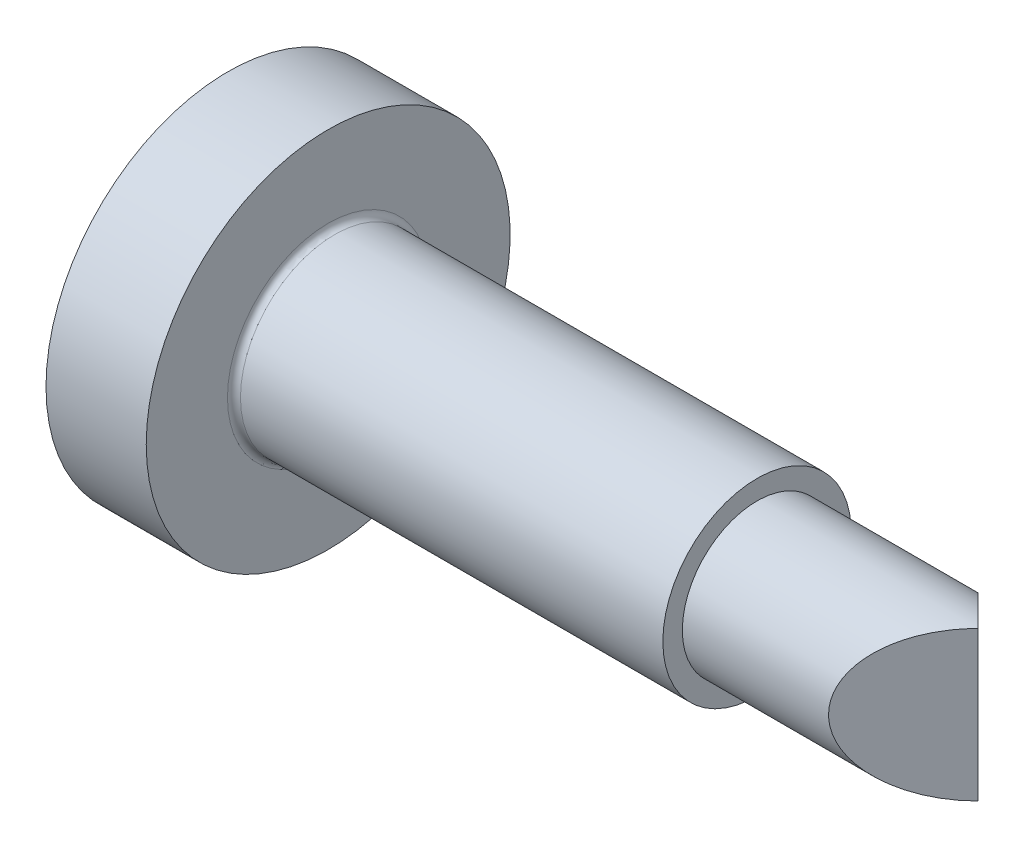
SolidWorks part; units mm, degrees
ref_plane "Front" through (0, 0, 0) normal (0, 0, 1) x (1, 0, 0)
ref_plane "Top" through (0, 0, 0) normal (0, 1, 0) x (1, 0, 0)
ref_plane "Right" through (0, 0, 0) normal (1, 0, 0) x (0, 0, -1)
sketch "Sketch1" plane through (0, 0, 0) normal (0, 0, 1) x (1, 0, 0)
  line L0 (-43.1593, 0) -> (76.0967, 0) construction
  line L1 (2.4, 1.45) -> (9, 1.45)
  line L2 (9, 1.45) -> (9, 1.15)
  line L3 (9, 1.15) -> (12.4, 1.15)
  line L4 (12.4, 1.15) -> (12.4, 0)
  line L5 (2.4, 1.45) -> (2.4, 2.8)
  line L6 (2.4, 2.8) -> (0.8575, 2.8)
  line L7 (12.4, 0) -> (0, 0)
  line L8 (3.5, 4.9815) -> (3.5, -1.8643) construction
  arc A0 (0.8575, 2.8) -> (0, 0) centre (5, 0) ccw
revolve "Base" add sketch "Sketch1" angle 360 about L0
cosmetic thread "ThreadCosmetic1" [suppressed] parameters "D1"=6.6, "D2"=2.3
fillet "Fillet1" radius 0.1 1 edges at (2.4, 0, 1.45)
sketch "Sketch2" plane through (0, 0, 0) normal (0, 1, 0) x (1, 0, 0)
  line L0 (7.7693, 0) -> (13.786, 0) construction
  line L2 (12.4, 0) -> (11.25, 1.15)
  line L4 (11.25, 1.15) -> (11.25, 1.8746)
  line L5 (11.25, 1.8746) -> (12.7585, 1.8746)
  line L6 (12.7585, 1.8746) -> (12.7585, -1.8746)
  line L8 (11.25, -1.8746) -> (12.7585, -1.8746)
  line L9 (11.25, -1.15) -> (11.25, -1.8746)
  line L10 (12.4, 0) -> (11.25, -1.15)
  line L11 (12.4, -1.15) -> (12.4, 1.15) construction
  line L12 (12.4, 1.15) -> (9, 1.15) construction
  point P14 (12.7585, 0)
  dimension "D1" = 45
  dimension "D2" = 0.7246
  dimension "D3" = 0.3585
extrude "Cut-Extrude1" cut sketch "Sketch2" against normal through all and the other way through all
sketch "Sketch3" plane through (0, 0, 0) normal (1, 0, 0) x (0, 0, -1)
  line L0 (-3.4533, 0) -> (3.7479, 0) construction
  line L1 (0, 3.3142) -> (0, -3.2487) construction
  line L2 (-0.3, 0.3) -> (-1.5, 0.3)
  line L3 (0.3, -1.5) -> (-0.3, -1.5)
  line L4 (0.3, -1.5) -> (0.3, -0.3)
  line L5 (0.3, 1.5) -> (-0.3, 1.5)
  line L6 (-0.3, -1.5) -> (-0.3, -0.3)
  line L7 (1.5, 0.3) -> (0.3, 0.3)
  line L8 (1.5, 0.3) -> (1.5, -0.3)
  line L9 (1.5, -0.3) -> (0.3, -0.3)
  line L10 (-1.5, 0.3) -> (-1.5, -0.3)
  line L11 (0.3, 0.3) -> (0.3, 1.5)
  line L12 (-0.3, 0.3) -> (-0.3, 1.5)
  line L13 (-0.3, -0.3) -> (-1.5, -0.3)
  dimension "D1" = 3
  dimension "D3" = 0.6
  dimension "D4" = 0.6
extrude "CrossRecess" cut sketch "Sketch3" along normal blind 0.8
fillet "Fillet2" radius 0.3 4 edges at (0.409, 0.3, 0.3) (0.409, 0.3, -0.3) (0.409, -0.3, 0.3) (0.409, -0.3, -0.3)
draft "Draft1" type of draft neutral plane draft angle 25 neutral plane "Right" faces to draft 4 face at (0.5175, -1.5, 0) face at (0.5175, 0, -1.5) face at (0.5175, 0, 1.5) face at (0.5175, 1.5, 0) neutral plane through (0, 0, 0) neutral plane normal (1, 0, 0) reverse direction yes parameters "D1"=25
sketch "Sketch4" plane through (0, 0, 0) normal (1, 0, 0) x (0, 0, -1)
  line L0 (-13.501, 0) -> (14.0755, 0) construction
  line L1 (0, -11.8062) -> (0, 13.0127) construction
  line L2 (0, 0) -> (-7.5165, 7.5165) construction
  line L3 (0, 0) -> (7.3653, 7.3653) construction
  line L4 (0, 0.4483) -> (1.0607, 1.0607)
  line L5 (0, 0.4483) -> (-1.0607, 1.0607)
  line L6 (1.0607, 1.0607) -> (0.4483, 0)
  line L7 (-1.0607, 1.0607) -> (-0.4483, 0)
  line L8 (-1.0607, -1.0607) -> (-0.4483, 0)
  line L9 (1.0607, -1.0607) -> (0.4483, 0)
  line L10 (0, -0.4483) -> (-1.0607, -1.0607)
  line L11 (0, -0.4483) -> (1.0607, -1.0607)
  dimension "D1" = 45
  dimension "D2" = 15
  dimension "D3" = 3
extrude "Cut-Extrude3" cut sketch "Sketch4" along normal blind 0.8
sketch "Sketch5" plane through (0, 0, 0) normal (0, 0, 1) x (1, 0, 0)
  line L0 (3.3268, 1.7964) -> (3.6732, 1.7964)
  line L1 (3.6732, 1.7964) -> (3.6732, 1.45)
  line L2 (3.6732, 1.45) -> (3.5, 1.15)
  line L3 (3.5, 1.15) -> (3.3268, 1.45)
  line L4 (3.3268, 1.7964) -> (3.3268, 1.45)
  line L5 (0, 0) -> (5.8873, 0) construction
  line L6 (2.4, -2.8) -> (2.4, 2.8) construction
  dimension "D2" = 2.3
  dimension "D1" = 2.9
  dimension "D3" = 1.1
revolve "Cut-Revolve10" [suppressed] cut sketch "Sketch5" angle 360 about L5
pattern_linear "LPattern10" [suppressed] count 13 spacing 0.45 along (1, 0, 0) of bodies 105
equation "\"D4@Sketch3\" = \"D3@Sketch3\""
equation "\"D3@Sketch3\" = \"m@Sketch3\" / 5"
equation "\"D1@Sketch3\" = \"m@Sketch3\""
equation "\"D1@CrossRecess\" = \"k@Sketch1\"  / 3"
equation "\"D1@Cut-Extrude3\" = \"D1@CrossRecess\""
equation "\"D1@Fillet2\" = \"D4@Sketch3\" / 2"
equation "\"D3@Sketch4\" = \"m@Sketch3\""
equation "\"D2@ThreadCosmetic1\" = \"dp@Sketch1\""
equation "\"D1@ThreadCosmetic1\" = \"lg@Sketch1\""
equation "\"D1@Sketch5\" = \"d@Sketch1\""
equation "\"D2@Sketch5\" = \"dp@Sketch1\""
equation "\"D3@Sketch5\" = \"a@Sketch1\""
equation "\"D3@LPattern10\" =  ( \"d@Sketch1\" - \"dp@Sketch1\" ) /2*1.5"
equation "\"D1@LPattern10\" = (  \"lg@Sketch1\" - \"a@Sketch1\" )  / \"D3@LPattern10\"  + 1"
